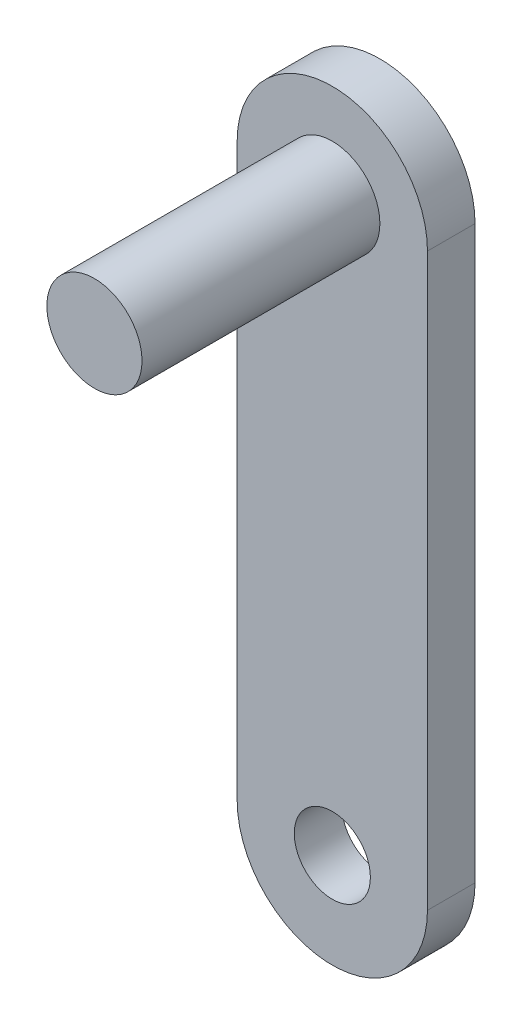
SolidWorks part; units mm, degrees
ref_plane "Front Plane" through (0, 0, 0) normal (0, 0, 1) x (1, 0, 0)
ref_plane "Top Plane" through (0, 0, 0) normal (0, 1, 0) x (1, 0, 0)
ref_plane "Right Plane" through (0, 0, 0) normal (1, 0, 0) x (0, 0, -1)
sketch "Sketch1" plane through (0, 0, 0) normal (0, 0, 1) x (1, 0, 0)
  line L2 (10, 30) -> (10, -30)
  line L4 (-10, 30) -> (-10, -30)
  line L5 (10, 30) -> (-10, -30) construction
  line L6 (10, -30) -> (-10, 30) construction
  arc A0 (-10, -30) -> (10, -30) centre (0, -30) ccw
  arc A1 (-10, 30) -> (10, 30) centre (0, 30) cw
  circle A2 centre (0, 30) radius 5
  circle A3 centre (0, -30) radius 4
  point P0 (0, 0)
  dimension "D3" = 10
  dimension "D4" = 8
  dimension "D5" = 10
  dimension "D1" = 20
  dimension "D2" = 60
extrude "Boss-Extrude1" add sketch "Sketch1" along normal blind 5
extrude "Boss-Extrude2" add sketch "Sketch1<2>" along normal blind 30 contours A2 region at (0, 30, 0)
sketch "Sketch1<2>" plane through (0, 0, 0) normal (0, 0, 1) x (1, 0, 0) same geometry as "Sketch1"
